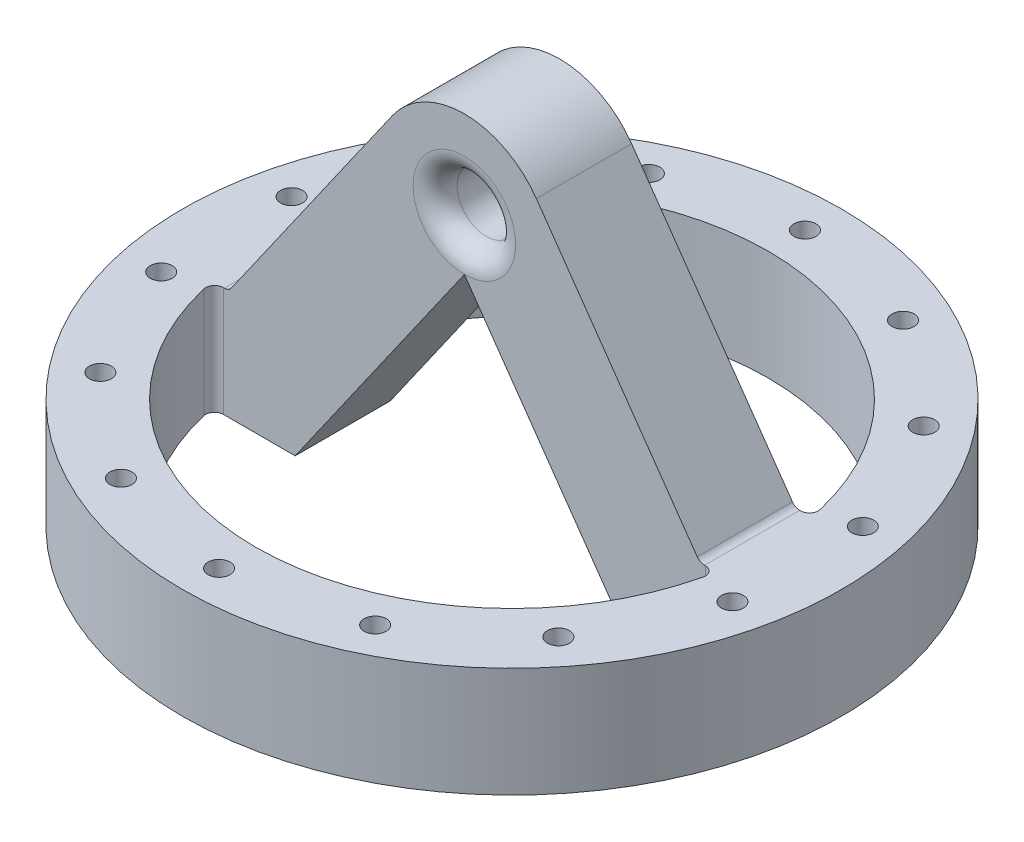
SolidWorks part; units mm, degrees
material "PBT Общее назначение"
ref_plane "Спереди" through (0, 0, 0) normal (0, 0, 1) x (1, 0, 0)
ref_plane "Сверху" through (0, 0, 0) normal (0, 1, 0) x (1, 0, 0)
ref_plane "Справа" through (0, 0, 0) normal (1, 0, 0) x (0, 0, -1)
sketch "Эскиз1" plane through (0, 0, 0) normal (0, 1, 0) x (1, 0, 0)
  line L0 (0, 0) -> (0, 45) construction
  circle A0 centre (0, 0) radius 45
  circle A1 centre (0, 0) radius 35
  circle A2 centre (0, 0) radius 40 construction
  circle A3 centre (0, 40) radius 1.5
  circle A4 centre (17.3553, 36.0388) radius 1.5
  circle A5 centre (31.2733, 24.9396) radius 1.5
  circle A6 centre (38.9971, 8.9008) radius 1.5
  circle A7 centre (38.9971, -8.9008) radius 1.5
  circle A8 centre (31.2733, -24.9396) radius 1.5
  circle A9 centre (17.3553, -36.0388) radius 1.5
  circle A10 centre (0, -40) radius 1.5
  circle A11 centre (-17.3553, -36.0388) radius 1.5
  circle A12 centre (-31.2733, -24.9396) radius 1.5
  circle A13 centre (-38.9971, -8.9008) radius 1.5
  circle A14 centre (-38.9971, 8.9008) radius 1.5
  circle A15 centre (-31.2733, 24.9396) radius 1.5
  circle A16 centre (-17.3553, 36.0388) radius 1.5
  point P37 (0, 0)
  dimension "D1" = 90
  dimension "D2" = 70
  dimension "D3" = 80
  dimension "D4" = 3
  dimension "D5" = 14
extrude "Бобышка-Вытянуть1" add sketch "Эскиз1" along normal blind 15
sketch "Эскиз2" plane through (0, 0, 0) normal (0, 0, 1) x (1, 0, 0)
  line L0 (0, 0) -> (0, 67.3561) construction
  line L1 (-36, 0) -> (-23.1068, 0)
  line L2 (-35, 0) -> (35, 0) construction
  line L4 (-45, 0) -> (45, 0) construction
  line L6 (-23.1068, 0) -> (0, 33)
  line L7 (-36, 15) -> (-32.1545, 15)
  line L8 (35, 15) -> (-35, 15) construction
  line L9 (-32.1545, 15) -> (-9.8298, 46.8829)
  line L11 (-36, 15) -> (-36, 0)
  line L12 (36, 0) -> (23.1068, 0)
  line L13 (36, 15) -> (36, 0)
  line L14 (36, 15) -> (32.1545, 15)
  line L15 (32.1545, 15) -> (9.8298, 46.8829)
  line L16 (23.1068, 0) -> (0, 33)
  circle A0 centre (0, 40) radius 4
  arc A1 (-9.8298, 46.8829) -> (9.8298, 46.8829) centre (0, 40) cw
  dimension "D1" = 8
  dimension "D2" = 55
  dimension "D6" = 36
  dimension "D3" = 12
  dimension "D4" = 7
extrude "Бобышка-Вытянуть2" add sketch "Эскиз2" along normal mid plane 13
fillet "Скругление1" radius 1.2 6 edges at (-34.3911, 7.5, 6.5) (-34.3911, 7.5, -6.5) (-32.1545, 15, 0) (34.3911, 7.5, 6.5) (32.1545, 15, 0) (34.3911, 7.5, -6.5)
fillet "Скругление2" radius 3 2 edges at (4, 40, -6.5) (4, 40, 6.5)
